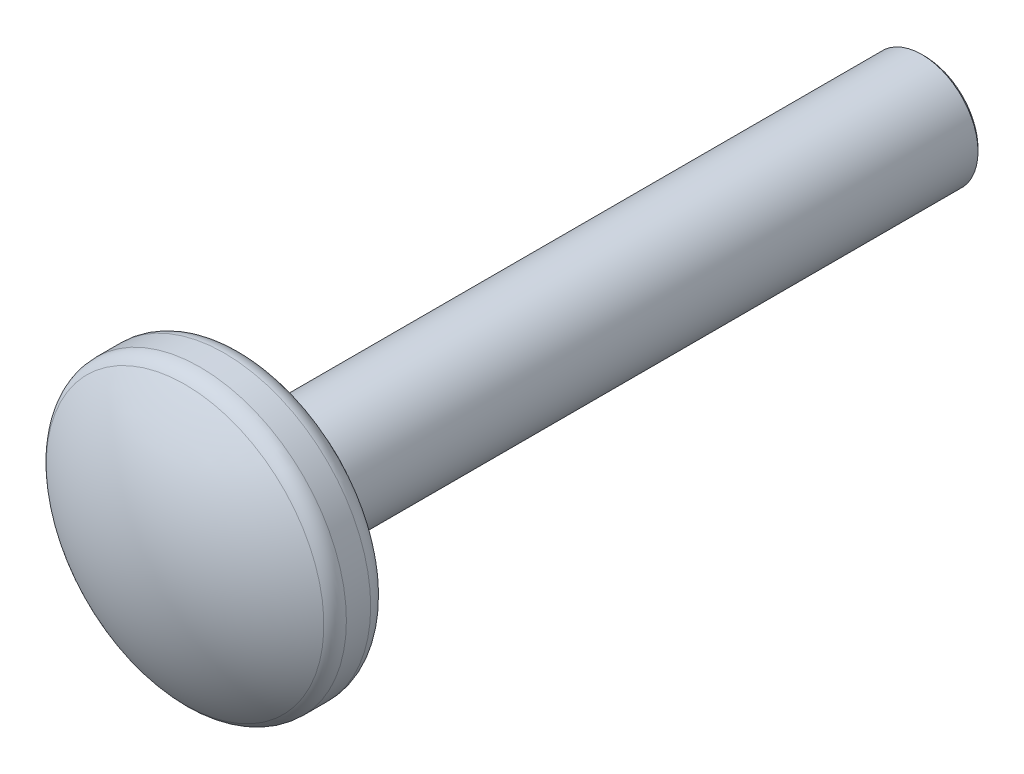
SolidWorks part; units mm, degrees
material "AISI 304"
ref_plane "Front Plane" through (0, 0, 0) normal (0, 0, 1) x (1, 0, 0)
ref_plane "Top Plane" through (0, 0, 0) normal (0, 1, 0) x (1, 0, 0)
ref_plane "Right Plane" through (0, 0, 0) normal (1, 0, 0) x (0, 0, -1)
sketch "Sketch1" plane through (0, 0, 0) normal (0, 0, 1) x (1, 0, 0)
  circle A0 centre (0, 0) radius 2.0828
  dimension "decimal equ" = 4.1656
curve "Helix/Spiral1" pitch 0.7937 height 19.8438 turns 25 parameters "helix length"=19.8438, "pitch"=0.7937
sketch "Sketch2" plane through (0, 0, 0) normal (1, 0, 0) x (0, 0, -1)
  line L0 (0.2977, 2.0828) -> (0.3969, 2.0828)
  line L1 (0.3969, 2.0828) -> (0.6945, 1.5672)
  line L2 (0.2977, 2.0828) -> (0, 1.5672)
  line L3 (0, 1.5672) -> (0.6945, 1.5672)
  line L4 (0.3473, 2.0828) -> (0.3473, 1.5672) construction
  line L6 (0.1488, 1.825) -> (0.5457, 1.825) construction
  line L7 (0, 1.5672) -> (0, 2.0828) construction
  line L8 (0, 2.0828) -> (0, -2.0828) construction
  line L9 (0, 2.0828) -> (0, -2.0828) construction
  point P8 (-3.2742, -2.0828)
  dimension "D1" = 60
  dimension "D3" = 0.0992
  dimension "D4" = 0.3969
  dimension "D2" = 3.2742
sketch "Sketch3" plane through (0, 0, 0) normal (1, 0, 0) x (0, 0, -1)
  line L0 (0, 0) -> (-19.05, 0) construction
  line L1 (0, 1.5672) -> (0.6945, 1.5672) construction
  line L2 (0, 0) -> (-19.05, 0)
  line L3 (0, 0) -> (0, 1.5672)
  line L4 (0, 1.5672) -> (-19.05, 1.5672)
  line L5 (-19.05, 0) -> (-19.05, 1.5672)
  dimension "length" = 19.05
revolve "Revolve1" add sketch "Sketch3" angle 360 about L0
sweep "Sweep1" [suppressed] add profiles "Sketch2" path "Helix/Spiral1"
sketch "Sketch39" plane through (0, 0, 0) normal (0, 0, -1) x (-1, 0, 0)
  circle A0 centre (0, 0) radius 2.0828 construction
  circle A1 centre (0, 0) radius 2.0828
extrude "Extrude5" [suppressed] cut sketch "Sketch39" along normal through all
sketch "Sketch38" plane through (0, 0, 0) normal (0, 0, -1) x (-1, 0, 0)
  circle A2 centre (0, 0) radius 1.4875
  circle A3 centre (0, 0) radius 1.4875
extrude "Extrude6" cut sketch "Sketch38" against normal through all draft 45 flip side to cut
sketch "Sketch10" plane through (0, 0, 0) normal (1, 0, 0) x (0, 0, -1)
  line L0 (0, 0) -> (23.0169, 0) construction
  line L1 (-273.05, 12.7) -> (-19.05, 12.7)
  line L2 (-273.05, 12.7) -> (-273.05, 0)
  line L3 (-273.05, 0) -> (-19.05, 0)
  line L4 (-19.05, 12.7) -> (-19.05, 0)
  line L5 (-19.05, 0) -> (-19.05, 1.5672) construction
  dimension "D1" = 254
  dimension "D2" = 12.7
revolve "Cut-Revolve2" [suppressed] cut sketch "Sketch10" angle 360 about L0
sketch "Sketch41" plane through (0, 0, 0) normal (1, 0, 0) x (0, 0, -1)
  line L0 (-19.05, 2.0828) -> (-19.05, 1.5672)
  line L1 (-19.05, 1.5672) -> (-18.1737, 1.5672)
  line L2 (-18.1737, 1.5672) -> (-17.6581, 2.0828)
  line L3 (-19.05, 2.0828) -> (-17.6581, 2.0828)
  line L4 (0, 1.5672) -> (0.6945, 1.5672) construction
  dimension "D1" = 0.8763
  dimension "D2" = 45
revolve "Cut-Revolve4" [suppressed] cut sketch "Sketch41" angle 360 about L2
sketch "Sketch8" plane through (0, 0, 0) normal (1, 0, 0) x (0, 0, -1)
  line L0 (0, 0) -> (-6.2449, 0) construction
  line L1 (-21.971, 0) -> (-19.05, 0)
  line L2 (-21.971, 0) -> (-21.971, 4.0894)
  line L3 (-21.971, 4.0894) -> (-19.05, 4.0894)
  line L4 (-19.05, 0) -> (-19.05, 4.0894)
  line L5 (-21.971, -4.0894) -> (-19.05, -4.0894) construction
  line L6 (-19.05, 0) -> (-19.05, 1.5672) construction
  dimension "head dia" = 8.1788
  dimension "head height" = 2.921
revolve "Revolve2" add sketch "Sketch8" angle 360 about L0
sketch "Sketch11" plane through (0, 0, 0) normal (1, 0, 0) x (0, 0, -1)
  line L0 (-20.5105, 4.0894) -> (-20.5105, -4.0894) construction
  line L1 (-21.971, 0) -> (-6.8951, 0) construction
  line L2 (-21.971, 4.0894) -> (-19.05, 4.0894) construction
  line L3 (-21.971, 0) -> (-21.971, 4.0894) construction
  line L4 (-20.2549, 4.0894) -> (-19.5758, 4.0894)
  line L6 (-19.05, 0) -> (-19.05, 4.0894) construction
  line L7 (-19.05, 3.5636) -> (-18.415, 3.5636)
  line L8 (-18.415, 3.5636) -> (-18.415, 4.7244)
  line L9 (-18.415, 4.7244) -> (-22.606, 4.7244)
  line L10 (-22.606, 4.7244) -> (-22.606, 0)
  line L11 (-22.606, 0) -> (-21.971, 0)
  arc A0 (-20.6751, 3.8796) -> (-21.971, 0) centre (-15.5156, 0) ccw
  arc A1 (-19.05, 3.5636) -> (-19.5758, 4.0894) centre (-19.5758, 3.5636) ccw
  arc A2 (-20.6751, 3.8796) -> (-20.2549, 4.0894) centre (-20.2549, 3.5636) cw
  dimension "D1" = 0.5258
  dimension "D2" = 0.635
  dimension "D3" = 0.635
  dimension "D4" = 0.635
revolve "Cut-Revolve3" cut sketch "Sketch11" angle 360 about L1
ref_plane "Plane1" through (0, 0, 21.971) normal (0, 0, 1) x (1, 0, 0)
sketch "Sketch12" plane through (0, 0, 21.971) normal (0, 0, 1) x (1, 0, 0)
  line L0 (0.508, 2.3264) -> (0.508, 1.1906)
  line L1 (0.508, 1.1906) -> (1.1906, 0.508) construction
  line L2 (1.1906, 0.508) -> (2.3264, 0.508)
  line L3 (0, 2.3813) -> (0, 0)
  line L4 (0, 0) -> (2.3813, 0)
  line L5 (0, 0) -> (0, 4.0894) construction
  line L6 (0, 0) -> (0.8493, 0.8493) construction
  line L7 (1.1906, 0) -> (1.1906, 1.5633) construction
  line L8 (0.508, 1.1906) -> (0.7079, 0.7079)
  line L9 (1.1906, 0.508) -> (0.7079, 0.7079)
  line L10 (0, 0) -> (0, -1.0114) construction
  line L11 (-0.508, 2.3264) -> (-0.508, 1.1906) construction
  arc A0 (2.3813, 0) -> (2.3264, 0.508) centre (0, 0) ccw
  arc A1 (0.508, 2.3264) -> (0, 2.3813) centre (0, 0) ccw
  arc A2 (-2.3813, 0) -> (-2.3264, 0.508) centre (0, 0) cw construction
  dimension "phillips dia" = 4.7625
  dimension "D2" = 45
  dimension "D4" = 22.5
  dimension "slot width" = 1.016
extrude "Cut-Extrude1" [suppressed] cut sketch "Sketch12" against normal blind 2.4829
draft "Draft3" [suppressed] type of draft neutral plane draft angle 15 neutral plane "Plane1" faces to draft 2 parameters "D1"=15
draft "Draft4" [suppressed] type of draft neutral plane draft angle 5 neutral plane "Plane1" faces to draft 4 parameters "D1"=5
pattern_circular "CirPattern1" [suppressed] count 4 over 360 about axis through (0, 0, 21.971) along (0, 0, -1) of bodies 110
ref_plane "Plane8" through (0, 0, 18.8939) normal (0, 0, -1) x (-1, 0, 0)
sketch "Sketch18" plane through (0, 0, 18.8939) normal (0, 0, 1) x (1, 0, 0)
  line L0 (0, 0) -> (0, 4.064) construction
  line L1 (1.5672, 0) -> (4.064, 0) construction
  circle A0 centre (0, 0) radius 4.064
  circle A1 centre (0, 0) radius 1.5672 construction
  circle A2 centre (0, 0) radius 1.5672 construction
  circle A3 centre (0, 0) radius 2.6908
  circle A4 centre (0, 0) radius 2.0828 construction
  point P8 (2.6908, 0)
  point P10 (0, 2.6908)
  dimension "washer dia." = 8.128
  dimension "D2" = 1.1235
sketch "Sketch21" plane through (0, 0, 18.8939) normal (0, 0, 1) x (1, 0, 0)
  circle A0 centre (0, 0) radius 2.6908
  circle A1 centre (0, 0) radius 1.5672
  circle A2 centre (0, 0) radius 2.0828 construction
extrude "Extrude2" add sketch "Sketch21" against normal blind 0.5842 separate body
ref_plane "Plane9" through (0, 2.6908, 0) normal (0, 1, 0) x (-1, 0, 0)
sketch "Sketch31" plane through (0, 2.6908, 0) normal (0, 1, 0) x (-1, 0, 0)
  line L1 (-0.508, 18.8939) -> (0.508, 18.8939)
  line L2 (-0.508, 18.8939) -> (-0.508, 18.3097)
  line L3 (-0.508, 18.3097) -> (0.508, 18.3097)
  line L4 (0.508, 18.8939) -> (0.508, 18.3097)
  line L5 (-2.6908, 18.3097) -> (2.6908, 18.3097) construction
  line L6 (0, 0) -> (0, 18.8939) construction
  line L7 (0.508, 18.6018) -> (-0.508, 18.6018) construction
  line L8 (0, 18.8939) -> (0, 18.3097) construction
  line L9 (2.6908, 18.8939) -> (-2.6908, 18.8939) construction
  dimension "D1" = 1.016
ref_plane "Plane10" through (0, 4.064, 0) normal (0, 1, 0) x (-1, 0, 0)
sketch "Sketch32" plane through (0, 4.064, 0) normal (0, 1, 0) x (-1, 0, 0)
  line L0 (-0.3775, 19.05) -> (-0.5773, 18.501)
  line L1 (-0.3775, 19.05) -> (0.5773, 18.7025)
  line L2 (-0.5773, 18.501) -> (0.3775, 18.1535)
  line L3 (0.5773, 18.7025) -> (0.3775, 18.1535)
  line L4 (-0.508, 18.8939) -> (-0.508, 18.3097) construction
  line L5 (-0.508, 18.3097) -> (0.508, 18.3097) construction
  line L6 (0.0999, 18.8763) -> (0, 18.6018) construction
  line L7 (0, 18.6018) -> (0.4774, 18.428) construction
  line L8 (0.508, 18.6018) -> (-0.508, 18.6018) construction
  line L9 (0, 0) -> (0, 6.2449) construction
  line L10 (-1.5672, 18.3097) -> (1.5672, 18.3097) construction
  dimension "D1" = 20
sketch "Sketch33" plane through (0, 2.6908, 0) normal (0, 1, 0) x (-1, 0, 0)
  line L1 (1.5672, 18.8939) -> (-1.5672, 18.8939) construction
  line L4 (0.508, 18.8939) -> (-0.508, 18.8939)
  line L5 (0.508, 18.3097) -> (0.508, 18.8939)
  line L6 (-0.508, 18.3097) -> (0.508, 18.3097)
  line L7 (-0.508, 18.8939) -> (-0.508, 18.3097)
  line L8 (0.508, 18.8939) -> (-0.508, 18.8939)
  line L9 (0.508, 18.3097) -> (0.508, 18.8939)
  line L10 (-0.508, 18.3097) -> (0.508, 18.3097)
  line L11 (-0.508, 18.8939) -> (-0.508, 18.3097)
  dimension "D1" = 0
extrude "Extrude3" add sketch "Sketch33" against normal up to next (1.1235 mm away)
loft "Loft2" [suppressed] add profiles "Sketch32", "Sketch31"
pattern_circular "CirPattern4" [suppressed] count 12 over 360 of bodies 186
sketch "Sketch40" plane through (0, 0, 0) normal (1, 0, 0) x (0, 0, -1)
  line L0 (-18.8939, 4.064) -> (-18.3097, 4.064) construction
  line L1 (-18.8939, -4.064) -> (-18.3097, -4.064) construction
  line L2 (-18.6018, 4.064) -> (-18.6018, -4.064) construction
  line L3 (-18.6018, 0) -> (0, 0) construction
  line L4 (0, -1.4875) -> (0, 1.4875) construction
  line L6 (-18.8939, -5.9931) -> (-18.8939, 5.9931) construction
  dimension "D1" = 0.5842
  dimension "D2" = 8.128
equation "\"D3@Sketch2\" = \"pitch@Helix/Spiral1\"*.125"
equation "\"D4@Sketch2\" = \"pitch@Helix/Spiral1\"*.5"
equation "\"D1@Sketch11\" = \"head height@Sketch8\"*.18"
equation "\"D1@Cut-Extrude1\" = \"head height@Sketch8\"*.85"
equation "\"D1@Sketch31\" = \"washer dia.@Sketch18\"*.125"
equation "\"helix length@Helix/Spiral1\" = \"length@Sketch3\" + \"pitch@Helix/Spiral1\""
equation "\"D1@Sketch38\" = \"pitch@Helix/Spiral1\"*.750"
equation "\"D1@Plane8\" = \"D2@Sketch32\""
equation "\"D2@Sketch18\" = \"D1@Sketch18\"*.45"
equation "\"D2@Sketch2\" = \"pitch@Helix/Spiral1\"*4.125"
equation "\"D1@Sketch40\" = \"washer width@Extrude2\""
equation "\"D2@Sketch40\" = \"washer dia.@Sketch18\""
equation "\"D1@Sketch41\" = \"washer width@Extrude2\"*1.50"
